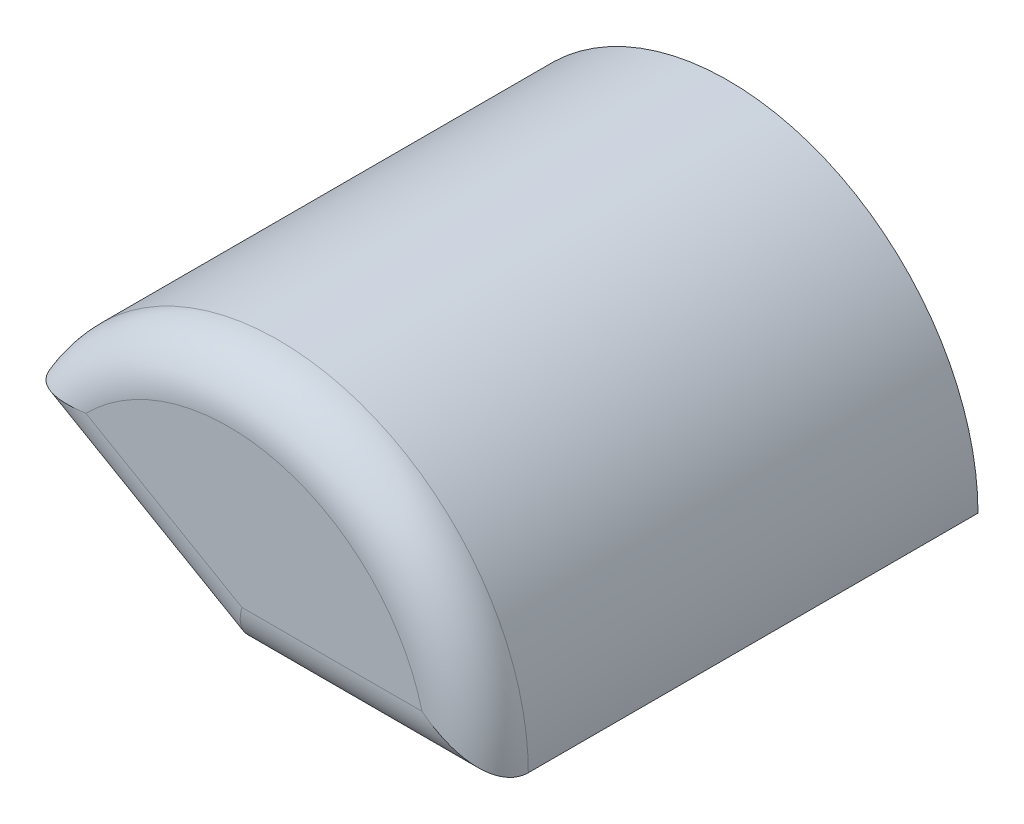
SolidWorks part; units mm, degrees
ref_plane "Front Plane" through (0, 0, 0) normal (0, 0, 1) x (1, 0, 0)
ref_plane "Top Plane" through (0, 0, 0) normal (0, 1, 0) x (1, 0, 0)
ref_plane "Right Plane" through (0, 0, 0) normal (1, 0, 0) x (0, 0, -1)
sketch "Sketch1" plane through (0, 0, 0) normal (0, 0, 1) x (1, 0, 0)
  line L0 (-4.3301, 2.5) -> (0, 0)
  line L1 (0, 0) -> (5, 0)
  arc A0 (5, 0) -> (-4.3301, 2.5) centre (0, 0) ccw
  dimension "D1" = 150
  dimension "D2" = 5
extrude "Boss-Extrude1" add sketch "Sketch1" along normal blind 10
fillet "Fillet1" radius 1 3 edges at (-2.1651, 1.25, 10) (1.2941, 4.8296, 10) (2.5, 0, 10)
equation "\"angle\"= 150"
equation "\"thicknes\"= 10"
equation "\"diameter\"= 5"
equation "\"D1@Sketch1\"= \"angle\""
equation "\"D2@Sketch1\"= \"diameter\""
equation "\"D1@Boss-Extrude1\"= \"thicknes\""
